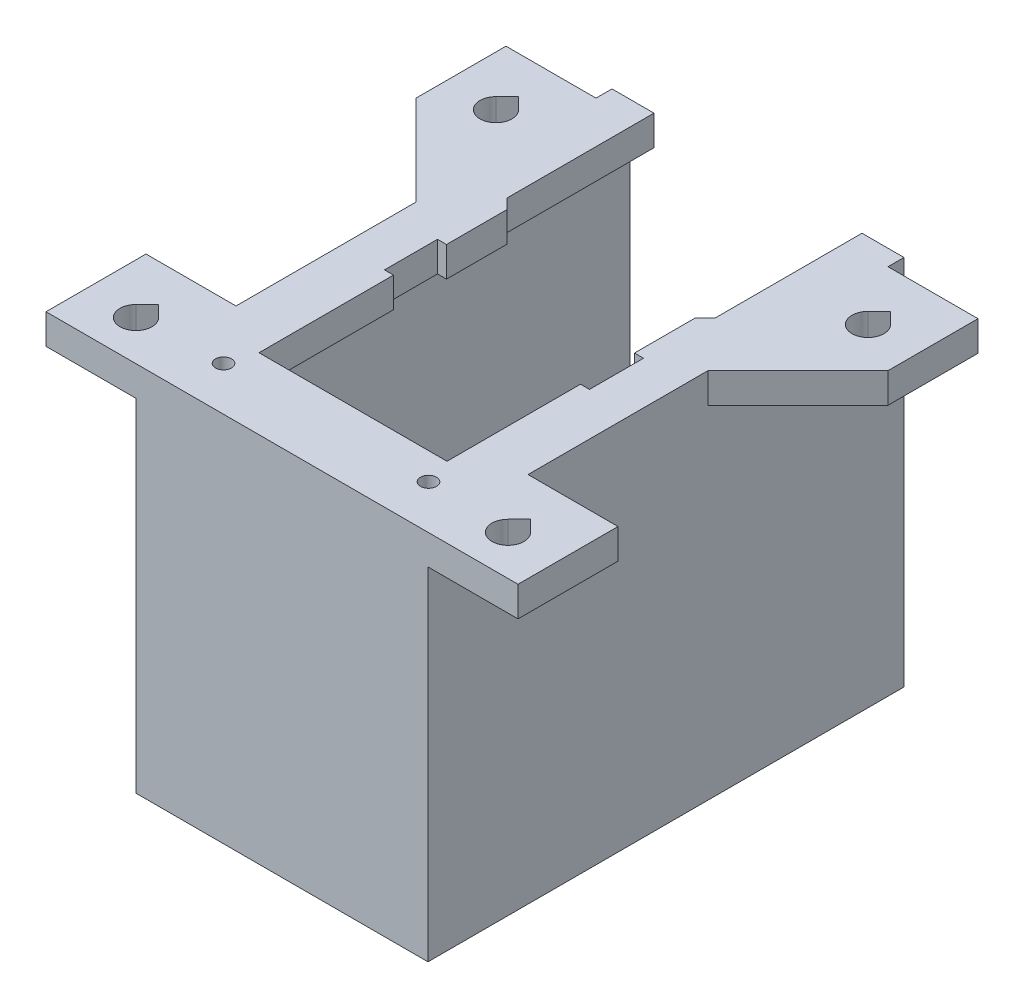
SolidWorks part; units mm, degrees
ref_plane "Front Plane" through (0, 0, 0) normal (0, 0, 1) x (1, 0, 0)
ref_plane "Top Plane" through (0, 0, 0) normal (0, 1, 0) x (1, 0, 0)
ref_plane "Right Plane" through (0, 0, 0) normal (1, 0, 0) x (0, 0, -1)
sketch "Sketch1" plane through (0, 0, 0) normal (0, 1, 0) x (1, 0, 0)
  line L0 (-9.2, -9.35) -> (9.2, -9.35) construction
  line L1 (-10.25, -12.25) -> (10.25, -12.25) construction
  line L2 (-10.25, -12.25) -> (-10.25, 12.25) construction
  line L3 (-10.25, 12.25) -> (10.25, 12.25) construction
  line L4 (10.25, -12.25) -> (10.25, 12.25) construction
  line L5 (-10.25, -12.25) -> (10.25, 12.25) construction
  line L6 (-10.25, 12.25) -> (10.25, -12.25) construction
  line L7 (0, -9.35) -> (0, 0) construction
  line L8 (-9.2, -9.35) -> (-9.2, 4) construction
  line L9 (-9.2, 4) -> (9.2, 4) construction
  line L10 (9.2, 4) -> (9.2, -9.35) construction
  line L11 (0, 8.05) -> (0, 0) construction
  line L12 (12.4, -14.65) -> (-12.4, -14.65) construction
  line L13 (12.4, -14.65) -> (12.4, 30.75) construction
  line L14 (12.4, 30.75) -> (-12.4, 30.75) construction
  line L15 (-12.4, -14.65) -> (-12.4, 30.75) construction
  line L16 (12.4, -14.65) -> (-12.4, 30.75) construction
  line L17 (12.4, 30.75) -> (-12.4, -14.65) construction
  line L18 (0, 20.55) -> (0, 8.05) construction
  line L19 (-9.4, -8.3) -> (-9.4, -16.65)
  line L20 (-7, -14.65) -> (7, -14.65) construction
  line L21 (-7, -14.65) -> (-7, 10.55) construction
  line L22 (-7, 10.55) -> (7, 10.55) construction
  line L23 (7, -14.65) -> (7, 10.55) construction
  line L24 (-7, -14.65) -> (7, 10.55) construction
  line L25 (-7, 10.55) -> (7, -14.65) construction
  line L26 (-14.6, -16.65) -> (14.6, -16.65)
  line L27 (-14.6, -16.65) -> (-14.6, 32.75)
  line L28 (-14.6, 32.75) -> (14.6, 32.75)
  line L29 (14.6, -16.65) -> (14.6, 32.75)
  line L30 (-14.6, -16.65) -> (14.6, 32.75) construction
  line L31 (-14.6, 32.75) -> (14.6, -16.65) construction
  line L32 (-12.8, -14.85) -> (12.8, -14.85)
  line L33 (-12.8, -14.85) -> (-12.8, 30.95)
  line L34 (-12.8, 30.95) -> (12.8, 30.95)
  line L35 (12.8, -14.85) -> (12.8, 30.95)
  line L36 (-12.8, -14.85) -> (12.8, 30.95) construction
  line L37 (-12.8, 30.95) -> (12.8, -14.85) construction
  line L38 (-7.2, -14.85) -> (7.2, -14.85) construction
  line L39 (-7.2, -14.85) -> (-7.2, 10.75)
  line L40 (-7.2, 10.75) -> (7.2, 10.75)
  line L41 (7.2, -14.85) -> (7.2, 10.75)
  line L42 (-7.2, -14.85) -> (7.2, 10.75) construction
  line L43 (-7.2, 10.75) -> (7.2, -14.85) construction
  line L44 (-9.4, -8.3) -> (9.4, -8.3) construction
  line L45 (-9.4, -8.3) -> (-9.4, 4.2)
  line L46 (-9.4, 4.2) -> (9.4, 4.2)
  line L47 (9.4, -8.3) -> (9.4, 4.2)
  line L48 (-9.4, -8.3) -> (9.4, 4.2) construction
  line L49 (-9.4, 4.2) -> (9.4, -8.3) construction
  line L50 (-7.2, -14.85) -> (-7.2, -16.65)
  line L51 (7.2, -14.85) -> (7.2, -16.65)
  line L52 (9.4, -8.3) -> (9.4, -16.65)
  line L53 (-12.8, -14.85) -> (-12.8, -16.65)
  line L54 (12.8, -14.85) -> (12.8, -16.65)
  line L55 (-12.8, -14.85) -> (-14.6, -14.85)
  line L56 (12.8, -14.85) -> (14.6, -14.85)
  line L57 (-10.3, 3.9) -> (-9.4, 3.9)
  line L58 (10.1, 9) -> (-10.1, 9) construction
  line L59 (10.1, 9) -> (10.1, 4) construction
  line L60 (10.1, 4) -> (-10.1, 4) construction
  line L61 (-10.1, 9) -> (-10.1, 4) construction
  line L62 (10.1, 9) -> (-10.1, 4) construction
  line L63 (10.1, 4) -> (-10.1, 9) construction
  line L64 (-10.3, 3.9) -> (-10.3, 9.2)
  line L65 (-10.3, 9.2) -> (10.3, 9.2)
  line L66 (10.3, 9.2) -> (10.3, 3.8)
  line L67 (10.3, 3.8) -> (9.4, 3.8)
  line L68 (-10.4, 30.95) -> (-10.4, 16.2422)
  line L69 (-10.4, 16.2422) -> (-4.9078, 10.75)
  line L70 (10.4, 16.2422) -> (4.9078, 10.75)
  line L71 (10.4, 30.95) -> (10.4, 16.2422)
  line L72 (-4.9078, 10.75) -> (-4.9078, 9.2)
  line L73 (4.9078, 10.75) -> (4.9078, 9.2)
  line L74 (-12.8, 30.95) -> (-12.8, 32.75)
  line L75 (12.8, 30.95) -> (12.8, 32.75)
  line L76 (-12.8, 30.95) -> (-14.6, 30.95)
  line L77 (12.8, 30.95) -> (14.6, 30.95)
  line L78 (-9.4, -9.55) -> (9.4, -9.55)
  line L79 (-9.4, 9.2) -> (-9.4, 15.2422)
  line L80 (9.4, 9.2) -> (9.4, 15.2422)
  line L81 (7.2, 10.75) -> (7.2, 13.0422)
  line L82 (-7.2, 10.75) -> (-7.2, 13.0422)
  circle A0 centre (-10.25, 12.25) radius 0.8
  circle A1 centre (10.25, 12.25) radius 0.8
  circle A2 centre (-10.25, -12.25) radius 0.8
  circle A3 centre (10.25, -12.25) radius 0.8
  circle A4 centre (0, 20.55) radius 10 construction
  circle A5 centre (0, 20.55) radius 10.4 construction
  circle A6 centre (-10.25, -8.45) radius 0.8
  circle A7 centre (10.25, -8.45) radius 0.8
  point P8 (0, 0)
  point P15 (0, -9.35)
  point P18 (0, 8.05)
  point P25 (0, -2.05)
  point P38 (0, -2.05)
  point P43 (0, -2.05)
  point P48 (0, 6.5)
  dimension "D1" = 1.6
  dimension "D9" = 2.4
  dimension "D11" = 20
  dimension "D27" = 0.2
  dimension "D30" = 6.2
  dimension "D2" = 24.5
  dimension "D3" = 20.5
  dimension "D4" = 18.4
  dimension "D5" = 2.9
  dimension "D6" = 13.35
  dimension "D7" = 24.8
  dimension "D8" = 45.4
  dimension "D10" = 10.2
  dimension "D12" = 14
  dimension "D13" = 1.8
  dimension "D14" = 1.8
  dimension "D15" = 0.4
  dimension "D16" = 0.4
  dimension "D17" = 0.2
  dimension "D18" = 0.2
  dimension "D19" = 0.2
  dimension "D20" = 0.2
  dimension "D21" = 5
  dimension "D22" = 20.2
  dimension "D23" = 0.2
  dimension "D24" = 0.2
  dimension "D25" = 0.2
  dimension "D26" = 45
  dimension "D28" = 0.2
  dimension "D29" = 0.2
extrude "Boss-Extrude2" add sketch "Sketch1" along normal blind 2 contours L33 L76 L27 L55 | L77 L35 L56 L29 | L56 L54 L26 L29 | L54 L32 L52 L26 | L52 L32 L41 L51 L26 | L51 L41 L32 L39 L50 L26 | L50 L39 L32 L19 L26 | L32 L53 L26 L19 | L53 L55 L27 L26 | L34 L71 L70 L40 L41 L65 L66 L47 L52 L32 L35 A3 A1 | L69 L68 L34 L33 L32 L19 L45 L64 L65 L39 L40 A2 A0 | L78 L19 L32 L39 | L78 L41 L32 L52 | L39 L82 L69 L79 L65 | L65 L64 L57 L45 L46 L39 | L19 L78 L39 L46 L45 | L41 L78 L52 L47 L46 | L67 L66 L65 L41 L46 L47 | L81 L41 L65 L80 L70 region at (-8.3, 0, 2.675) region at (-11.3268, 0, -6.8174) region at (-8.3, 0, 12.2) region at (-8.7688, 0, -6.6546) region at (-8.3, 0, 15.75) region at (-11.1, 0, 15.75) region at (-13.7, 0, -8.05) region at (-13.7, 0, 15.75) region at (0, 0, 15.75) region at (8.3, 0, 12.2) region at (8.3, 0, 2.675) region at (8.3, 0, 15.75) region at (-8.3816, 0, -11.7119) region at (8.775, 0, -6.6387) region at (11.3279, 0, -6.8195) region at (11.1, 0, 15.75) region at (8.3816, 0, -11.7119) region at (13.7, 0, 15.75) region at (13.7, 0, -8.05)
extrude "Boss-Extrude4" add sketch "Sketch1<6>" along normal offset from surface (35.2 mm away) 33.2 contours L33 L74 L28 L27 L55 | L77 L35 L56 L29 | L56 L54 L26 L29 | L54 L32 L52 L26 | L51 L41 L32 L39 L50 L26 | L32 L53 L26 L19 | L53 L55 L27 L26 | L50 L39 L32 L19 L26 | L52 L32 L41 L51 L26 region at (-8.3, 0, 15.75) region at (-11.1, 0, 15.75) region at (-13.7, 0, -8.05) region at (-13.7, 0, 15.75) region at (0, 0, 15.75) region at (8.3, 0, 15.75) region at (11.1, 0, 15.75) region at (13.7, 0, 15.75) region at (13.7, 0, -8.05) up to face at (0, 2, -9.9474) offset beyond the face yes
sketch "Sketch1<6>" plane through (0, 0, 0) normal (0, 1, 0) x (1, 0, 0) same geometry as "Sketch1"
extrude "Boss-Extrude7" add sketch "Sketch1<9>" along normal offset from surface (37.2 mm away) 2 contours L65 L79 L69 L68 L34 L33 L32 L19 L45 L57 L64 A2 A0 | L80 L65 L66 L67 L47 L52 L32 L35 L34 L71 L70 A3 A1 | L33 L76 L27 L55 | L53 L55 L27 L26 | L32 L53 L26 L19 | L50 L32 L19 L26 | L51 L32 L50 L26 | L52 L32 L51 L26 | L54 L32 L52 L26 | L56 L54 L26 L29 | L77 L35 L56 L29 | L78 L41 L32 L52 | L78 L19 L32 L39 | L78 L39 L32 L41 | A6 | A7 | A0 | A1 region at (-11.3268, 0, -6.8174) region at (-8.3, 0, 12.2) region at (-8.3, 0, 15.75) region at (-11.1, 0, 15.75) region at (0, 0, 12.2) region at (-13.7, 0, -8.05) region at (-13.7, 0, 15.75) region at (0, 0, 15.75) region at (8.3, 0, 12.2) region at (8.3, 0, 15.75) region at (11.3279, 0, -6.8195) region at (11.1, 0, 15.75) region at (13.7, 0, 15.75) region at (13.7, 0, -8.05) region at (-10.25, 0, -12.25) region at (10.25, 0, -12.25) region at (-10.25, 0, 8.45) region at (10.25, 0, 8.45) up to face at (0, 35.2, -7.6) offset beyond the face yes
sketch "Sketch1<9>" plane through (0, 0, 0) normal (0, 1, 0) x (1, 0, 0) same geometry as "Sketch1"
extrude "Cut-Extrude6" cut sketch "Sketch1<10>" along normal offset from surface (34.2 mm away) 3 contours L67 L66 L65 L41 L46 L47 | L65 L64 L57 L45 L46 L39 | L19 L78 L39 L46 L45 | L41 L78 L52 L47 L46 | L39 L82 L69 L79 L65 | L81 L41 L65 L80 L70 | L65 L79 L69 L68 L34 L33 L32 L19 L45 L57 L64 A2 A0 | L80 L65 L66 L67 L47 L52 L32 L35 L34 L71 L70 A3 A1 | L39 L78 L41 L46 | L78 L39 L32 L41 | L78 L19 L32 L39 | L78 L41 L32 L52 | A2 | A3 | A6 | A7 | A0 | A1 region at (-8.3, 0, 2.675) region at (-11.3268, 0, -6.8174) region at (-8.3, 0, 12.2) region at (-8.7688, 0, -6.6546) region at (0, 0, 12.2) region at (0, 0, 2.675) region at (8.3, 0, 12.2) region at (8.3, 0, 2.675) region at (-8.3816, 0, -11.7119) region at (8.775, 0, -6.6387) region at (11.3279, 0, -6.8195) region at (8.3816, 0, -11.7119) region at (-10.25, 0, -12.25) region at (10.25, 0, -12.25) region at (-10.25, 0, 12.25) region at (10.25, 0, 12.25) region at (-10.25, 0, 8.45) region at (10.25, 0, 8.45) up to face at (10.25, 37.2, 13.05)
sketch "Sketch1<10>" plane through (0, 0, 0) normal (0, 1, 0) x (1, 0, 0) same geometry as "Sketch1"
extrude "Boss-Extrude8" add sketch "Sketch1<11>" along normal offset from surface (2 mm away) 2 contours L80 L65 L66 L67 L47 L52 L32 L35 L34 L71 L70 A3 A1 | L78 L41 L32 L52 | L65 L79 L69 L68 L34 L33 L32 L19 L45 L57 L64 A2 A0 | L78 L19 L32 L39 | L67 L66 L65 L41 L46 L47 | L41 L78 L52 L47 L46 | L65 L64 L57 L45 L46 L39 | L19 L78 L39 L46 L45 | L39 L82 L69 L79 L65 | L81 L41 L65 L80 L70 | A3 | A2 region at (-8.3, 0, 2.675) region at (-11.3268, 0, -6.8174) region at (-8.3, 0, 12.2) region at (-8.7688, 0, -6.6546) region at (8.3, 0, 12.2) region at (8.3, 0, 2.675) region at (-8.3816, 0, -11.7119) region at (8.775, 0, -6.6387) region at (11.3279, 0, -6.8195) region at (8.3816, 0, -11.7119) region at (-10.25, 0, 12.25) region at (10.25, 0, 12.25) up to face at (0, 0, -7.6)
sketch "Sketch1<11>" plane through (0, 0, 0) normal (0, 1, 0) x (1, 0, 0) same geometry as "Sketch1"
sketch "Sketch2" plane through (0, 37.2, 0) normal (0, 1, 0) x (1, 0, 0)
  line L0 (-18.6, 23.35) -> (18.6, 23.35) construction
  line L1 (0, 23.35) -> (0, 0) construction
  line L2 (-14.6, 29.35) -> (-23.6, 29.35)
  line L3 (-14.6, -16.65) -> (-14.6, 30.95) construction
  line L4 (-23.6, 29.35) -> (-23.6, 21.35)
  line L5 (-23.6, 21.35) -> (-14.6, 21.35)
  line L6 (-14.6, 21.35) -> (-14.6, 29.35)
  line L7 (23.6, 29.35) -> (23.6, 21.35)
  line L8 (23.6, 21.35) -> (14.6, 21.35)
  line L9 (14.6, 21.35) -> (14.6, 29.35)
  line L10 (14.6, 29.35) -> (23.6, 29.35)
  line L12 (-19.7314, 24.4814) -> (-18.6, 25.6127)
  line L13 (-18.6, 25.6127) -> (-17.4686, 24.4814)
  line L14 (-18.6, 25.6127) -> (-18.6, 23.35) construction
  line L15 (19.7314, 24.4814) -> (18.6, 25.6127)
  line L16 (18.6, 25.6127) -> (17.4686, 24.4814)
  line L17 (-14.6, -16.65) -> (-23.6, -16.65)
  line L18 (-23.6, -16.65) -> (-23.6, -6.65)
  line L19 (-23.6, -6.65) -> (-14.6, -6.65)
  line L20 (-18.6, -12.65) -> (-18.6, 23.35) construction
  line L21 (-18.6, -10.3873) -> (-19.7314, -11.5186)
  line L22 (-18.6, -10.3873) -> (-17.4686, -11.5186)
  line L23 (-14.6, -16.65) -> (-14.6, -6.65)
  line L24 (18.6, -10.3873) -> (19.7314, -11.5186)
  line L25 (18.6, -10.3873) -> (17.4686, -11.5186)
  line L26 (14.6, -16.65) -> (14.6, -6.65)
  line L27 (14.6, -16.65) -> (23.6, -16.65)
  line L28 (23.6, -16.65) -> (23.6, -6.65)
  line L29 (23.6, -6.65) -> (14.6, -6.65)
  line L30 (-14.6, -16.65) -> (14.6, -16.65) construction
  circle A0 centre (-18.6, 23.35) radius 1.6
  circle A1 centre (18.6, 23.35) radius 1.6
  circle A2 centre (-18.6, -12.65) radius 1.6
  circle A3 centre (18.6, -12.65) radius 1.6
  line M11 (-14.6, 30.95) -> (-14.6, -16.65)
  line M13 (14.6, -16.65) -> (14.6, 30.95)
  dimension "D1" = 3.2
  dimension "D2" = 4
  dimension "D3" = 5
  dimension "D7" = 90
  dimension "D8" = 4
  dimension "D9" = 6
  dimension "D11" = 36
  dimension "D4" = 6
  dimension "D5" = 90
  dimension "D6" = 2
  dimension "D10" = 5
extrude "Boss-Extrude9" add sketch "Sketch2" against normal blind 3 contours L10 L8 L7 A1 M13 | L4 L5 L2 A0 L12 L13 M11 | L19 L18 L17 A2 L21 L22 M11 | L28 L29 L27 L24 A3 L25 M13 region at (-19.1678, 37.2, -25.6058) region at (-14.7345, 37.2, 11.65) region at (19.1, 37.2, 6.7845) region at (19.1678, 37.2, -25.6058)
chamfer "Chamfer1" distance 10 angle 45 2 edges at (14.6, 35.7, -21.35) (-14.6, 35.7, -21.35)
